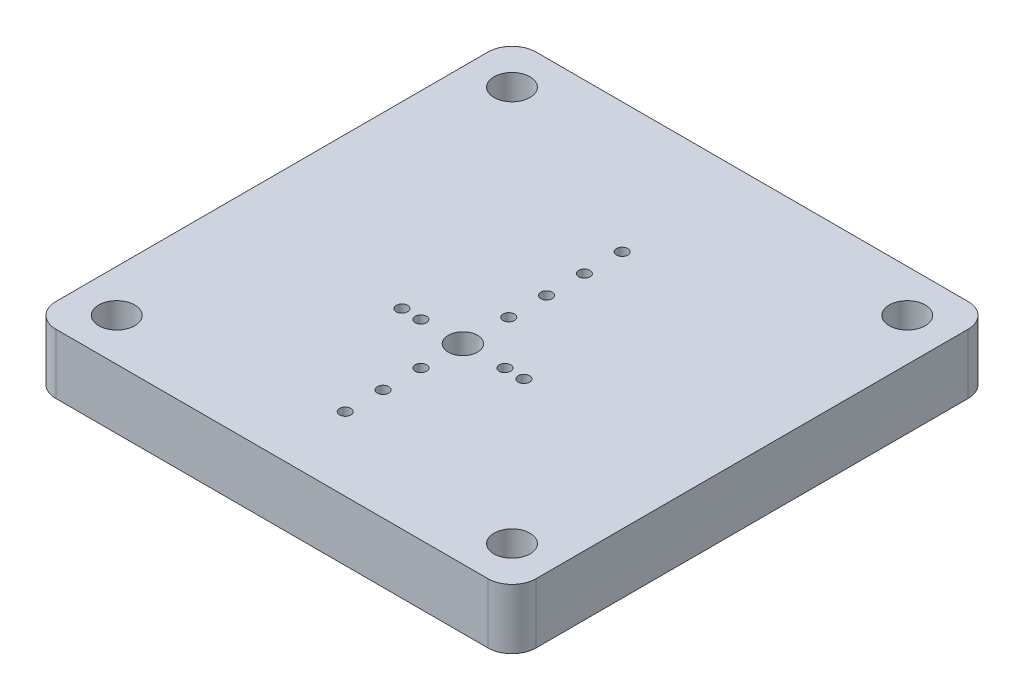
SolidWorks part; units mm, degrees
material "ABS PC"
ref_plane "Front Plane" through (0, 0, 0) normal (0, 0, 1) x (1, 0, 0)
ref_plane "Top Plane" through (0, 0, 0) normal (0, 1, 0) x (1, 0, 0)
ref_plane "Right Plane" through (0, 0, 0) normal (1, 0, 0) x (0, 0, -1)
sketch "Sketch1" plane through (0, 0, 0) normal (0, 1, 0) x (1, 0, 0)
  line L0 (0, 50.8) -> (4.4901, 46.3099)
  line L1 (0, 0) -> (50.8, 0)
  line L2 (0, 0) -> (0, 50.8)
  line L3 (0, 50.8) -> (50.8, 50.8)
  line L4 (50.8, 0) -> (50.8, 50.8)
  line L5 (0, 25.4) -> (50.8, 25.4) construction
  line L6 (25.4, 50.8) -> (25.4, 0) construction
  circle A0 centre (4.4901, 46.3099) radius 1.905
  circle A1 centre (4.4901, 4.4901) radius 1.905
  circle A2 centre (46.3099, 4.4901) radius 1.905
  circle A3 centre (46.3099, 46.3099) radius 1.905
  circle A4 centre (25.404, 11.752) radius 0.6 construction
  circle A5 centre (18.954, 20.202) radius 0.6 construction
  circle A6 centre (20.954, 20.202) radius 0.6 construction
  circle A7 centre (31.854, 20.202) radius 0.6 construction
  circle A8 centre (29.854, 20.202) radius 0.6 construction
  circle A9 centre (25.404, 37.052) radius 0.6 construction
  circle A10 centre (25.404, 33.052) radius 0.6 construction
  circle A11 centre (25.404, 29.052) radius 0.6 construction
  circle A12 centre (25.404, 25.052) radius 0.6 construction
  circle A13 centre (25.404, 7.752) radius 0.6 construction
  circle A14 centre (25.404, 15.752) radius 0.6 construction
  circle A15 centre (25.404, 20.202) radius 1.55 construction
  circle A16 centre (25.404, 11.752) radius 0.6
  circle A17 centre (18.954, 20.202) radius 0.6
  circle A18 centre (20.954, 20.202) radius 0.6
  circle A19 centre (31.854, 20.202) radius 0.6
  circle A20 centre (29.854, 20.202) radius 0.6
  circle A21 centre (25.404, 37.052) radius 0.6
  circle A22 centre (25.404, 33.052) radius 0.6
  circle A23 centre (25.404, 29.052) radius 0.6
  circle A24 centre (25.404, 25.052) radius 0.6
  circle A25 centre (25.404, 7.752) radius 0.6
  circle A26 centre (25.404, 15.752) radius 0.6
  circle A27 centre (25.404, 20.202) radius 1.55
  dimension "D1" = 3.81
  dimension "D2" = 50.8
  dimension "D3" = 50.8
  dimension "D4" = 6.35
extrude "Boss-Extrude1" add sketch "Sketch1" along normal blind 6.35 contours A0 L2 L1 L4 L3 A1 A2 A3 region at (25.4, 0, -50.0816)
sketch "Sketch2" plane through (0, 0, 0) normal (0, 1, 0) x (1, 0, 0)
  line L0 (4.4901, 44.2975) -> (4.4901, 6.5025)
  line L1 (6.5025, 4.4901) -> (44.2975, 4.4901)
  line L2 (46.3099, 44.2975) -> (46.3099, 6.5025)
  line L3 (44.2975, 46.3099) -> (6.5025, 46.3099)
  circle A0 centre (4.4901, 46.3099) radius 1.905
  circle A1 centre (4.4901, 46.3099) radius 2.0124
  circle A2 centre (46.3099, 46.3099) radius 1.905
  circle A3 centre (46.3099, 46.3099) radius 2.0124
  circle A4 centre (46.3099, 4.4901) radius 1.905
  circle A5 centre (46.3099, 4.4901) radius 2.0124
  circle A6 centre (4.4901, 4.4901) radius 1.905
  circle A7 centre (4.4901, 4.4901) radius 2.0124
extrude "Cut-Extrude1" [suppressed] cut sketch "Sketch2" along normal blind 1.5875 from surface contours A7 L1 A5 L2 A3 L3 A1 L0 starting at face at (4.4901, 0, -44.4049)
sketch "Sketch3" plane through (0, 0, 0) normal (0, 1, 0) x (1, 0, 0)
  line L0 (3.2513, 44.2975) -> (3.2513, 6.5025)
  line L1 (6.5025, 3.2513) -> (44.2975, 3.2513)
  line L2 (47.5487, 44.2975) -> (47.5487, 6.5025)
  line L3 (44.2975, 47.5487) -> (6.5025, 47.5487)
  circle A0 centre (3.2513, 47.5487) radius 1.905
  circle A1 centre (3.2513, 47.5487) radius 3.2513
  circle A2 centre (47.5487, 47.5487) radius 1.905
  circle A3 centre (47.5487, 47.5487) radius 3.2513
  circle A4 centre (47.5487, 3.2513) radius 1.905
  circle A5 centre (47.5487, 3.2513) radius 3.2513
  circle A6 centre (3.2513, 3.2513) radius 1.905
  circle A7 centre (3.2513, 3.2513) radius 3.2513
extrude "Cut-Extrude2" [suppressed] cut sketch "Sketch3" against normal blind 1.5875 from surface contours A7 L1 A5 L2 A3 L3 A1 L0 starting at face at (4.4901, 6.35, -44.4049)
fillet "Fillet1" radius 2.54 4 edges at (50.8, 3.175, -50.8) (50.8, 3.175, 0) (0, 3.175, 0) (0, 3.175, -50.8)
sketch "Sketch4" plane through (0, 0, 0) normal (0, -1, 0) x (1, 0, 0)
  line L4 (10.2051, -4.4901) -> (40.5949, -4.4901)
  line L5 (46.3099, -10.2051) -> (46.3099, -40.5949)
  line L6 (40.5949, -46.3099) -> (10.2051, -46.3099)
  line L7 (4.4901, -40.5949) -> (4.4901, -10.2051)
  arc A4 (4.4901, -10.2051) -> (10.2051, -4.4901) centre (4.4901, -4.4901) ccw
  arc A5 (40.5949, -4.4901) -> (46.3099, -10.2051) centre (46.3099, -4.4901) ccw
  arc A6 (46.3099, -40.5949) -> (40.5949, -46.3099) centre (46.3099, -46.3099) ccw
  arc A7 (10.2051, -46.3099) -> (4.4901, -40.5949) centre (4.4901, -46.3099) ccw
  circle A8 centre (4.4901, -4.4901) radius 1.905
  dimension "D1" = 11.43
extrude "Cut-Extrude3" cut sketch "Sketch4" against normal blind 3.175
